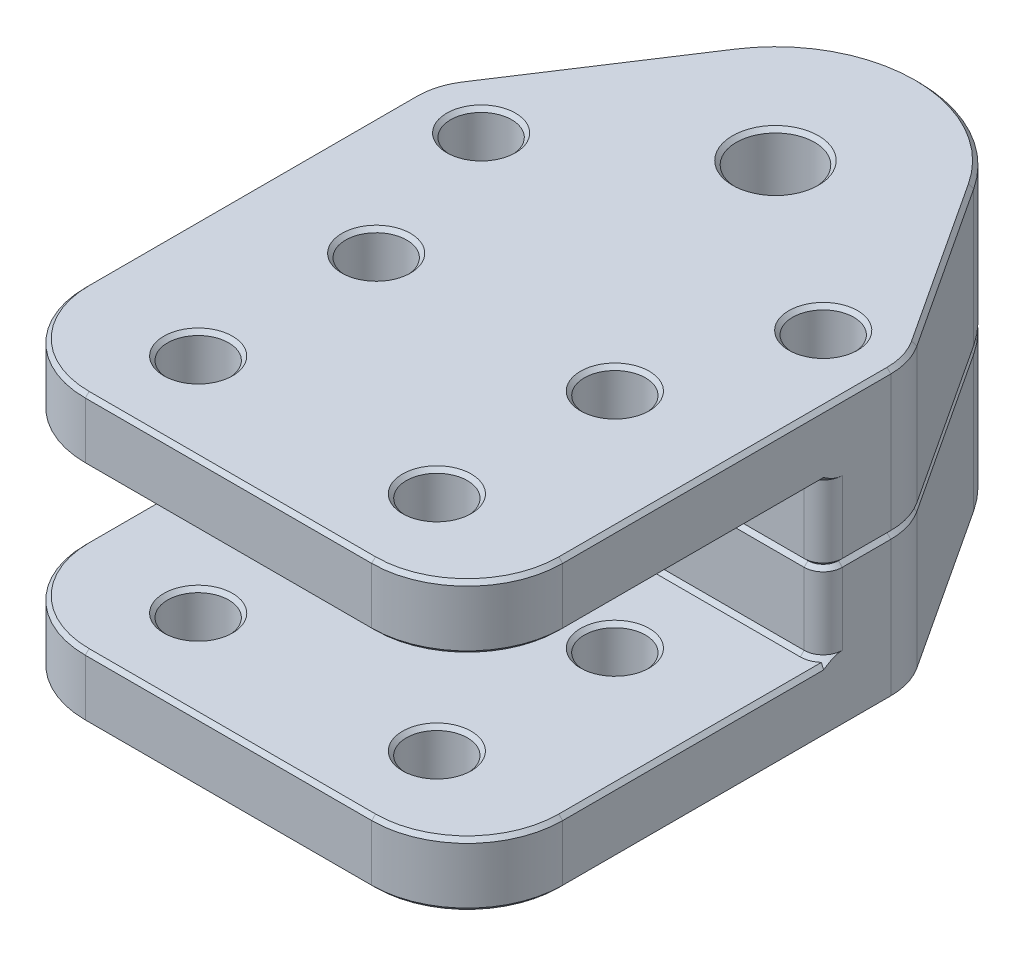
SolidWorks part; units mm, degrees
ref_plane "Front Plane" through (0, 0, 0) normal (1, 0, 0) x (0, 1, 0)
ref_plane "Top Plane" through (0, 0, 0) normal (0, 0, 1) x (0, 1, 0)
ref_plane "Right Plane" through (0, 0, 0) normal (0, 1, 0) x (-1, 0, 0)
sketch "Sketch1" plane through (0, 0, 0) normal (1, 0, 0) x (0, 1, 0)
  line L0 (-8.33, 37.29) -> (-15, 37.29)
  line L1 (0, 0) -> (-8.33, 0)
  line L2 (0, 0) -> (0, 37.29)
  line L3 (0, 37.29) -> (-8.33, 37.29)
  line L4 (-8.33, 0) -> (-8.33, 37.29)
  line L5 (-15, 37.29) -> (-15, -35)
  line L6 (-15, -35) -> (0, -35)
  line L7 (0, -35) -> (0, 0)
  dimension "D1" = 8.33
  dimension "D2" = 37.29
  dimension "D3" = 35
  dimension "D4" = 15
extrude "Boss-Extrude1" add sketch "Sketch1" against normal blind 50 contours L6 L7 L1 L4 L0 L5 region at (0, -8.8389, -5.8807)
sketch "Sketch2" plane through (0, -15, 0) normal (0, -1, 0) x (1, 0, 0)
  line L0 (-50, -35) -> (0, -35) construction
  line L1 (-25, -35) -> (-25, 37.29)
  line L2 (-48.8428, -10.9655) -> (-37.5499, -28.2158)
  line L3 (-37.5, 37.29) -> (-37.5, 0) construction
  line L4 (0, -35) -> (0, 37.29)
  line L5 (0, 37.29) -> (-50, 37.29)
  line L6 (-50, 37.29) -> (-50, -35)
  line L7 (-50, -35) -> (0, -35)
  line L8 (0, -35) -> (0, 37.29)
  line L9 (0, 37.29) -> (-50, 37.29)
  line L10 (-50, 37.29) -> (-50, -35)
  line L11 (-50, -35) -> (0, -35)
  line L12 (0, -35) -> (0, 0)
  line L13 (-50, -35) -> (0, -35)
  line L14 (-50, 0) -> (-50, -35)
  line L15 (0, 0) -> (-50, 0)
  line L16 (0, -35) -> (0, 0)
  line L17 (-50, -35) -> (0, -35)
  line L18 (-50, 0) -> (-50, -35)
  line L19 (0, 0) -> (-50, 0)
  line L20 (-50, 37.29) -> (-50, -35) construction
  line L21 (-1.1572, -10.9655) -> (-12.4501, -28.2158)
  line L22 (-12.5, 37.29) -> (-12.5, 0) construction
  circle A0 centre (-25, -20) radius 4.1
  circle A1 centre (-25, -20) radius 15
  circle A2 centre (-42.915, -7.085) radius 7.085
  circle A3 centre (-42.915, -7.085) radius 3.2
  circle A4 centre (-7.085, -7.085) radius 7.085
  circle A5 centre (-7.085, -7.085) radius 3.2
  circle A6 centre (-37.5, 27.9675) radius 3.2
  circle A7 centre (-37.5, 9.3225) radius 3.2
  circle A8 centre (-12.5, 27.9675) radius 3.2
  circle A9 centre (-12.5, 9.3225) radius 3.2
  point P11 (-25, -35)
  line M11 (0, -35) -> (0, 37.29)
  line M14 (-50, -35) -> (0, -35)
  dimension "D3" = 8.2
  dimension "D4" = 6.4
  dimension "D5" = 14.1699
  dimension "D8" = 6.4
  dimension "D12" = 30
  dimension "D6" = 25
  dimension "D7" = 12.5
  dimension "D9" = 37.29
  dimension "D10" = 9.3225
  dimension "D11" = 9.3225
  dimension "D1" = 0
  dimension "D2" = 0
extrude "Cut-Extrude1" cut sketch "Sketch2" against normal through all contours A2 L18 A1 L2 M14 | A4 L21 A1 M11 M14 | A5 | L1 A0 | L1 A0 | A3 | A7 | A6 | A8 | A9 region at (-6.1534, -15, -26.6858) region at (-43.8466, -15, -26.6858) region at (-26.7401, -15, -20) region at (-23.2599, -15, -20) region at (-42.915, -15, -7.085) region at (-7.085, -15, -7.085) region at (-37.5, -15, 27.9675) region at (-37.5, -15, 9.3225) region at (-12.5, -15, 27.9675) region at (-12.5, -15, 9.3225)
fillet "Fillet1" radius 10 2 edges at (-50, -11.665, 37.29) (0, -11.665, 37.29)
fillet "Fillet2" radius 2 2 edges at (0, -4.165, 0) (-50, -4.165, 0)
chamfer "Chamfer1" distance 0.4 angle 45 34 edges at (-37.5, -8.33, 12.5225) (-37.5, -8.33, 31.1675) (-12.5, -8.33, 31.1675) (-12.5, -8.33, 12.5225) (-7.085, -15, -10.285) (-37.5, -15, 6.1225) (-37.5, -15, 24.7675) (-12.5, -15, 24.7675) (-12.5, -15, 6.1225) (-25, -15, -24.1) (-42.915, -15, -10.285) (-2.9289, -15, 34.3611) (0, -15, 10.1025) (-0.2955, -15, -9.1097) (-6.8037, -15, -19.5907) (-25, -15, -35) (-43.1963, -15, -19.5907) (-49.7045, -15, -9.1097) (-50, -15, 10.1025) (-47.0711, -15, 34.3611) (-25, -15, 37.29) (-49.4142, 0, -0.5858) (-50, 0, -4.5425) (-49.7045, 0, -9.1097) (-43.1963, 0, -19.5907) (-25, 0, -35) (-6.8037, 0, -19.5907) (-0.2955, 0, -9.1097) (0, 0, -4.5425) (-0.5858, 0, -0.5858) (-25, 0, 0) (-7.085, 0, -10.285) (-25, 0, -24.1) (-42.915, 0, -10.285)
chamfer "Chamfer2" distance 0.4 angle 45 3 edges at (-49.4142, -8.33, -0.5858) (-0.5858, -8.33, -0.5858) (-25, -8.33, 0)
chamfer "Chamfer3" distance 0.4 angle 45 5 edges at (-50, -8.33, 13.3083) (0, -8.33, 13.3083) (-47.0711, -8.33, 34.3611) (-2.9289, -8.33, 34.3611) (-25, -8.33, 37.29)
mirror "Mirror1" about plane through (-50, 0, 0) normal (0, 1, 0) of bodies 102
equation "\"D7@Sketch2\"=\"D6@Sketch2\"/2"
equation "\"D10@Sketch2\"=\"D9@Sketch2\"/4"
equation "\"D11@Sketch2\"=\"D10@Sketch2\""
